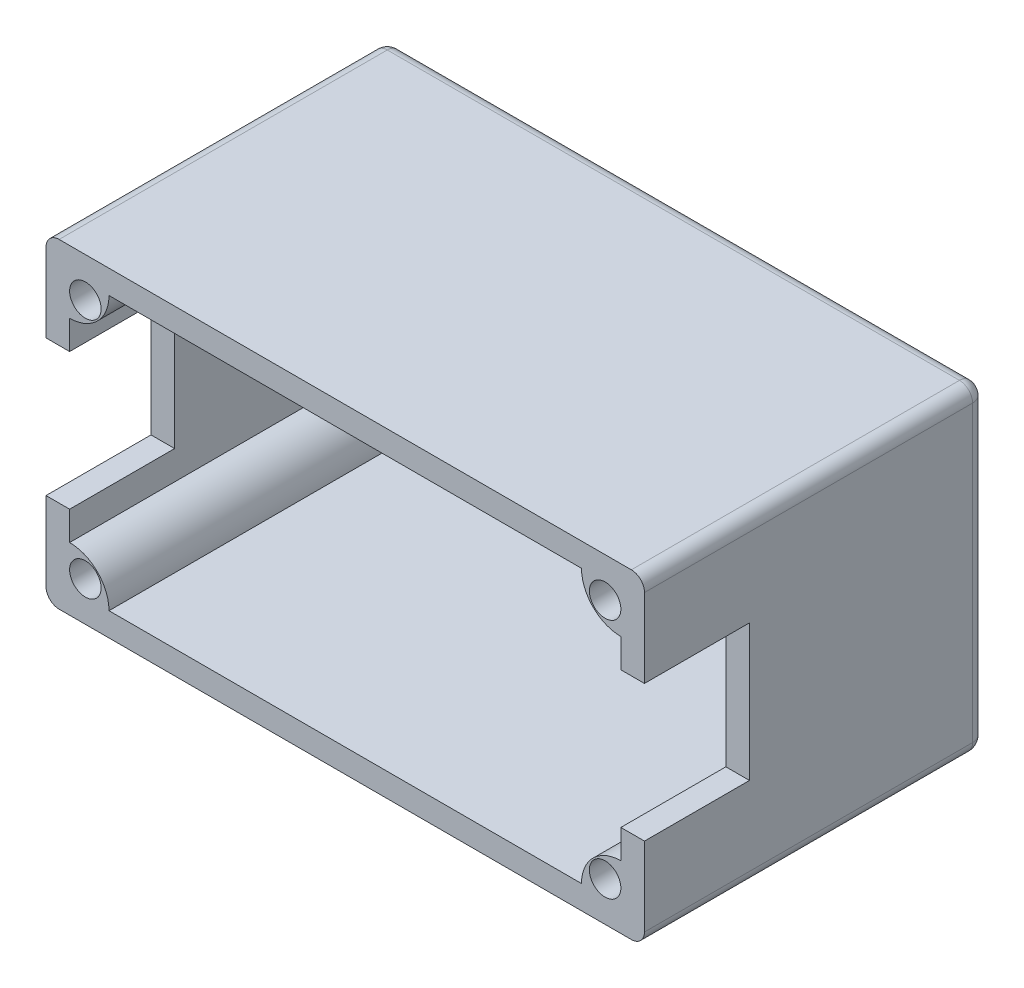
SolidWorks part; units mm, degrees
ref_plane "前视基准面" through (0, 0, 0) normal (0, 0, 1) x (1, 0, 0)
ref_plane "上视基准面" through (0, 0, 0) normal (0, 1, 0) x (1, 0, 0)
ref_plane "右视基准面" through (0, 0, 0) normal (1, 0, 0) x (0, 0, -1)
sketch "草图1" plane through (0, 0, 0) normal (0, 0, 1) x (1, 0, 0)
  line L1 (-11.4, 6.1) -> (11.4, 6.1)
  line L2 (-11.4, 6.1) -> (-11.4, -6.1)
  line L3 (-11.4, -6.1) -> (11.4, -6.1)
  line L4 (11.4, 6.1) -> (11.4, -6.1)
  line L5 (-11.4, 6.1) -> (11.4, -6.1) construction
  line L6 (-11.4, -6.1) -> (11.4, 6.1) construction
  point P0 (0, 0)
  dimension "D1" = 22.8
  dimension "D2" = 12.2
extrude "凸台-拉伸1" add sketch "草图1" along normal blind 13
sketch "草图2" plane through (0, 0, 13) normal (0, 0, 1) x (1, 0, 0)
  line L0 (11.4, 6.1) -> (-11.4, 6.1) construction
  line L1 (-10.5, 5.2) -> (10.5, 5.2)
  line L2 (-10.5, 5.2) -> (-10.5, -5.2)
  line L3 (-10.5, -5.2) -> (10.5, -5.2)
  line L4 (10.5, 5.2) -> (10.5, -5.2)
  line L5 (-11.4, 6.1) -> (-11.4, -6.1) construction
  line L6 (-11.4, -6.1) -> (11.4, -6.1) construction
  line L7 (11.4, -6.1) -> (11.4, 6.1) construction
  dimension "D1" = 0.9
  dimension "D2" = 0.9
  dimension "D3" = 0.9
  dimension "D4" = 0.9
extrude "切除-拉伸1" cut sketch "草图2" against normal blind 11
sketch "草图3" plane through (0, 0, 2) normal (0, 0, 1) x (1, 0, 0)
  line L0 (10.5, -5.2) -> (10.5, 5.2) construction
  line L1 (10.5, 5.2) -> (-10.5, 5.2) construction
  line L2 (10.5, -5.2) -> (10.5, 5.2) construction
  line L3 (-10.5, -5.2) -> (10.5, -5.2) construction
  line L4 (-10.5, 5.2) -> (-10.5, -5.2) construction
  circle A0 centre (9.9, 4.6) radius 0.6
  circle A1 centre (-9.9, -4.6) radius 0.6
  circle A2 centre (9.9, -4.6) radius 0.6
  circle A3 centre (-9.9, 4.6) radius 0.6
  dimension "D1" = 1.2
  dimension "D5" = 1.2
  dimension "D7" = 1.2
  dimension "D10" = 0.6
  dimension "D11" = 1.2
  dimension "D2" = 0.6
  dimension "D3" = 0.6
  dimension "D4" = 19.8
  dimension "D6" = 0.6
  dimension "D8" = 0.6
  dimension "D9" = 0.6
  dimension "D12" = 0.6
sketch "草图4" plane through (0, 0, 13) normal (0, 0, 1) x (1, 0, 0)
  line L0 (-11.4, 6.1) -> (-11.4, -6.1) construction
  line L1 (-11.4, 2.6) -> (-10.5, 2.6)
  line L2 (-11.4, 2.6) -> (-11.4, -2.6)
  line L3 (-11.4, -2.6) -> (-10.5, -2.6)
  line L4 (-10.5, 2.6) -> (-10.5, -2.6)
  line L5 (-10.5, 5.2) -> (-10.5, -5.2) construction
  line L6 (11.4, 6.1) -> (-11.4, 6.1) construction
  line L8 (-11.4, -6.1) -> (11.4, -6.1) construction
  dimension "D1" = 3.5
  dimension "D2" = 3.5
extrude "切除-拉伸2" cut sketch "草图4" against normal blind 4
fillet "圆角1" radius 0.5 4 edges at (0, 6.1, 0) (-11.4, 0, 0) (0, -6.1, 0) (11.4, 0, 0)
sketch "草图7" plane through (0, 0, 2) normal (0, 0, 1) x (1, 0, 0)
  line L0 (-5.85, -2.45) -> (5.15, -2.45) construction
  line L1 (-5.85, -0.2) -> (5.15, -0.2)
  line L2 (-5.85, -4.7) -> (5.15, -4.7)
  line L3 (-10.5, -5.2) -> (10.5, -5.2) construction
  line L5 (10.5, -5.2) -> (10.5, 5.2) construction
  arc A0 (-5.85, -0.2) -> (-5.85, -4.7) centre (-5.85, -2.45) ccw
  arc A1 (5.15, -4.7) -> (5.15, -0.2) centre (5.15, -2.45) ccw
  point P2 (-0.35, -2.45)
  point P7 (-8.1, -2.45)
  point P8 (7.4, -2.45)
  dimension "D2" = 15.5
  dimension "D1" = 11
  dimension "D3" = 0.5
  dimension "D4" = 10.85
extrude "切除-拉伸5" cut sketch "草图7" against normal blind 2
fillet "圆角2" radius 0.5 8 edges at (11.2536, 5.9536, 0.1464) (11.2536, -5.9536, 0.1464) (-11.2536, -5.9536, 0.1464) (-11.2536, 5.9536, 0.1464) (11.4, 6.1, 6.75) (11.4, -6.1, 6.75) (-11.4, -6.1, 6.75) (-11.4, 6.1, 6.75)
sketch "草图8" plane through (0, 0, 13) normal (0, 0, 1) x (1, 0, 0)
  line L0 (10.5, -5.2) -> (10.5, 5.2) construction
  line L1 (10.5, 2.6) -> (11.4, 2.6)
  line L2 (10.5, 2.6) -> (10.5, -2.6)
  line L3 (10.5, -2.6) -> (11.4, -2.6)
  line L4 (11.4, 2.6) -> (11.4, -2.6)
  line L5 (11.4, -5.6) -> (11.4, 5.6) construction
  line L6 (10.9, 6.1) -> (-10.9, 6.1) construction
  line L7 (-10.9, -6.1) -> (10.9, -6.1) construction
  dimension "D1" = 3.5
  dimension "D2" = 3.5
extrude "切除-拉伸6" cut sketch "草图8" against normal blind 4
sketch "草图10" plane through (0, 0, 2) normal (0, 0, 1) x (1, 0, 0)
  line L0 (-10.5, -2.6) -> (-10.5, -5.2) construction
  line L1 (-10.5, -5.2) -> (10.5, -5.2) construction
  line L2 (-10.5, 5.2) -> (-10.5, -5.2) construction
  line L3 (-10.5, -5.2) -> (10.5, -5.2) construction
  line L4 (10.5, 5.2) -> (-10.5, 5.2) construction
  line L5 (10.5, -5.2) -> (10.5, 5.2) construction
  line L6 (10.5, -5.2) -> (10.5, -2.6) construction
  line L7 (10.5, 5.2) -> (-10.5, 5.2) construction
  line L8 (-10.5, 5.2) -> (-10.5, 2.6) construction
  line L9 (-10.5, 3.7) -> (-10.5, 5.2)
  line L10 (10.5, 2.6) -> (10.5, 5.2) construction
  line L11 (9, 5.2) -> (10.5, 5.2)
  line L12 (10.5, 5.2) -> (10.5, 3.7)
  line L13 (-10.5, 5.2) -> (-9, 5.2)
  line L14 (10.5, -3.7) -> (10.5, -5.2)
  line L15 (10.5, -5.2) -> (9, -5.2)
  line L16 (-10.5, -3.7) -> (-10.5, -5.2)
  line L17 (-10.5, -5.2) -> (-9, -5.2)
  arc A0 (-10.5, -3.7) -> (-9, -5.2) centre (-10.5, -5.2) cw
  arc A1 (10.5, -3.7) -> (9, -5.2) centre (10.5, -5.2) ccw
  arc A2 (-9, 5.2) -> (-10.5, 3.7) centre (-10.5, 5.2) cw
  arc A3 (9, 5.2) -> (10.5, 3.7) centre (10.5, 5.2) ccw
  dimension "D3" = 1.5
  dimension "D6" = 1.5
  dimension "D7" = 1.5
  dimension "D9" = 1.5
  dimension "D10" = 1.5
  dimension "D12" = 1.5
  dimension "D1" = 1.5
  dimension "D2" = 1.5
  dimension "D4" = 1.5
  dimension "D5" = 1.5
  dimension "D8" = 1.5
  dimension "D11" = 1.5
extrude "凸台-拉伸2" add sketch "草图10" along normal blind 11
extrude "切除-拉伸8" cut sketch "草图3" along normal through all and the other way through all
sketch "草图9" plane through (0, 0, 0) normal (0, 0, -1) x (-1, 0, 0)
  circle A0 centre (-9.9, 4.6) radius 1.1
  circle A1 centre (9.9, 4.6) radius 1.1
  circle A2 centre (9.9, -4.6) radius 1.1
  circle A3 centre (-9.9, -4.6) radius 1.1
  dimension "D1" = 2.2
  dimension "D2" = 2.2
  dimension "D3" = 2.2
  dimension "D4" = 2.2
extrude "切除-拉伸9" cut sketch "草图9" against normal blind 0.5
